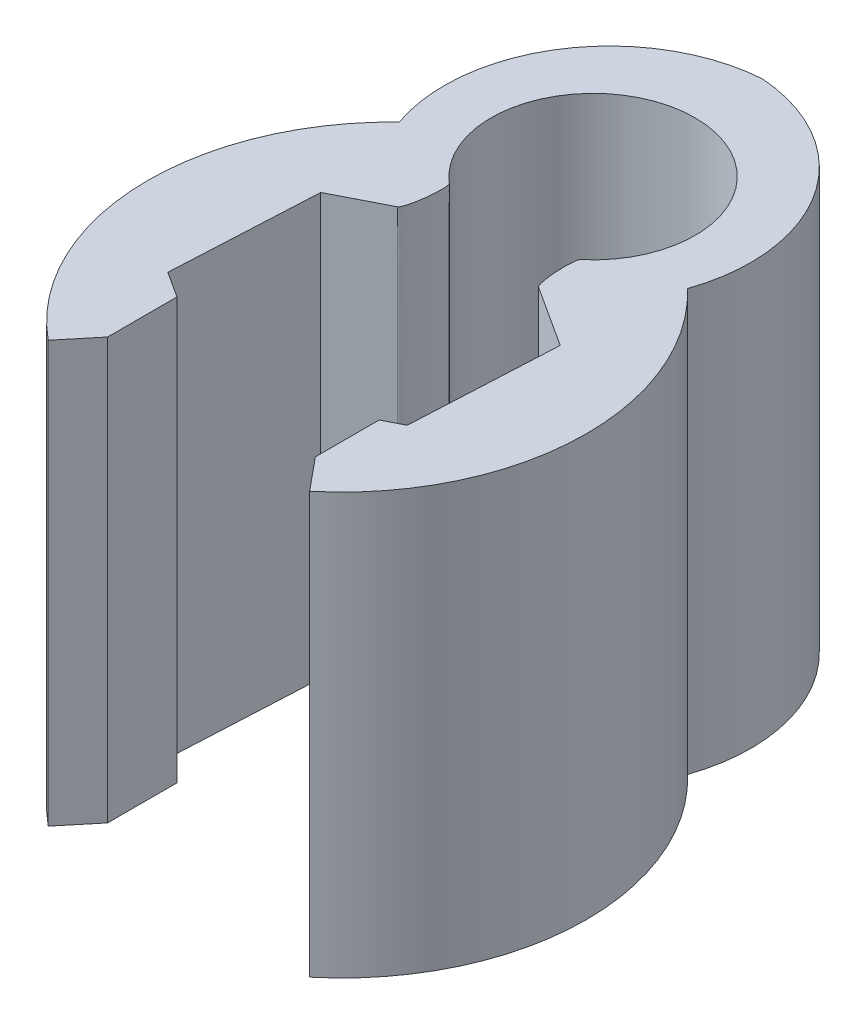
SolidWorks part; units mm, degrees
ref_plane "Front Plane" through (0, 0, 0) normal (0, 0, 1) x (1, 0, 0)
ref_plane "Top Plane" through (0, 0, 0) normal (0, 1, 0) x (1, 0, 0)
ref_plane "Right Plane" through (0, 0, 0) normal (1, 0, 0) x (0, 0, -1)
sketch "Sketch3" plane through (0, 0, 0) normal (0, 1, 0) x (1, 0, 0)
  line L0 (-7.2765, 0.1114) -> (11.8281, 0.1114) construction
  line L1 (-2.4796, 5.151) -> (-2.4796, 6.4742)
  line L2 (5.874, 3.0075) -> (0.3324, 6.5907)
  line L3 (0.3324, 6.5907) -> (-5.5415, 3.5833)
  line L4 (-5.5415, 3.5833) -> (-5.874, -3.0075)
  line L5 (-5.874, -3.0075) -> (-0.3324, -6.5907)
  line L6 (-0.3324, -6.5907) -> (5.5415, -3.5833)
  line L7 (5.5415, -3.5833) -> (5.874, 3.0075)
  line L8 (2.4796, 5.151) -> (2.4796, 6.4742)
  line L9 (-4.7012, -3.7658) -> (-4.7012, -6.9056)
  line L10 (-4.7012, -6.9056) -> (-5.9188, -8.3785)
  line L11 (0, 2.9063) -> (0, -1.8101) construction
  line L12 (4.7012, -6.9056) -> (5.9188, -8.3785)
  line L13 (4.7012, -3.7658) -> (4.7012, -6.9056)
  circle A0 centre (0, 0) radius 5.715 construction
  circle A1 centre (0, 10.3692) radius 4.6174
  arc A2 (-5.9188, -8.3785) -> (-6.5266, 8.121) centre (1.1246, 0.1419) cw
  arc A3 (-6.5266, 8.121) -> (0, 18.035) centre (0.5425, 10.5725) cw
  arc A4 (6.5266, 8.121) -> (0, 18.035) centre (-0.5425, 10.5725) ccw
  arc A5 (5.9188, -8.3785) -> (6.5266, 8.121) centre (-1.1246, 0.1419) ccw
  dimension "D1" = 11.43
  dimension "D2" = 0
extrude "Boss-Extrude1" add sketch "Sketch3" along normal blind 19.05 contours L12 A5 A4 A3 A2 L10 L9 L5 L4 L3 L1 A1 L8 L2 L7 L6 L13 | A1 L1 L3 | A1 L2 L8 region at (-4.1612, 0, -4.6613) region at (-2.0247, 0, -5.8096) region at (2.1055, 0, -5.8575)
fillet "Fillet6" radius 1.27 2 edges at (1.328, 9.525, -5.947) (-1.0635, 9.525, -5.876) conic radius 6.35
sketch "Sketch4" plane through (0, 19.05, 0) normal (0, 1, 0) x (1, 0, 0)
  line L1 (-6.1573, 3.9814) -> (-6.5266, -3.3416)
  line L2 (-6.5266, -3.3416) -> (-0.3694, -7.323)
  line L3 (-0.3694, -7.323) -> (6.1573, -3.9814)
  line L4 (6.1573, -3.9814) -> (6.5266, 3.3416)
  line L5 (6.5266, 3.3416) -> (0.3694, 7.323)
  line L6 (0.3694, 7.323) -> (-6.1573, 3.9814)
  circle A0 centre (0, 0) radius 6.35 construction
